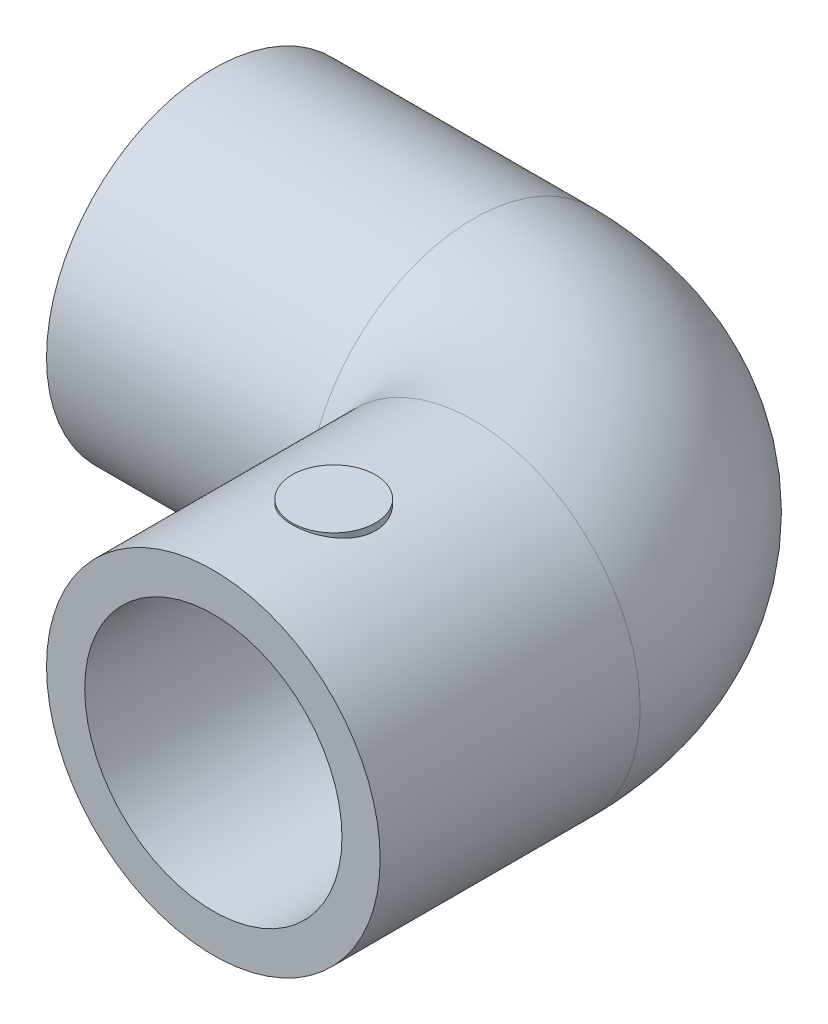
SolidWorks part; units mm, degrees
material "PVC Rígido"
ref_plane "Alzado" through (0, 0, 0) normal (0, 0, 1) x (1, 0, 0)
ref_plane "Planta" through (0, 0, 0) normal (0, 1, 0) x (1, 0, 0)
ref_plane "Vista lateral" through (0, 0, 0) normal (1, 0, 0) x (0, 0, -1)
sketch "Croquis1" plane through (0, 0, 0) normal (0, 1, 0) x (1, 0, 0)
  line L0 (-36.125, 0) -> (-14.5, 0)
  line L1 (0, -14.5) -> (0, -36.125)
  arc A0 (-14.5, 0) -> (0, -14.5) centre (-14.5, -14.5) cw
  point P6 (0, 0)
  dimension "D3" = 14.5
  dimension "D1" = 36.125
  dimension "D2" = 36.125
ref_plane "Plano1" through (0, 0, 36.125) normal (0, 0, 1) x (1, 0, 0)
sketch "Croquis2" plane through (0, 0, 36.125) normal (0, 0, 1) x (1, 0, 0)
  circle A0 centre (0, 0) radius 13.875
  circle A1 centre (0, 0) radius 10.7
  dimension "D1" = 27.75
  dimension "D2" = 21.4
sweep "Barrer1" add profiles "Croquis2" path "Croquis1"
sketch "Croquis3" plane through (0, 0, 36.125) normal (0, 0, 1) x (1, 0, 0)
  circle A0 centre (0, 0) radius 10.0034
  circle A1 centre (0, 0) radius 10.7
  circle A2 centre (0, 0) radius 10.7 construction
extrude "Saliente-Extruir1" add sketch "Croquis3" against normal blind 1 from offset 22.5 offset against normal yes
sketch "Croquis5" plane through (-36.125, 0, 0) normal (-1, 0, 0) x (0, 0, 1)
  circle A0 centre (0, 0) radius 9.6972
  circle A1 centre (0, 0) radius 10.7
  circle A2 centre (0, 0) radius 10.7 construction
extrude "Saliente-Extruir2" add sketch "Croquis5" along normal blind 1 from offset 22.5 offset against normal yes
sketch "Croquis6" plane through (0, 0, 0) normal (0, 1, 0) x (1, 0, 0)
  circle A0 centre (0, -26.1093) radius 3.4666
extrude "Saliente-Extruir3" add sketch "Croquis6" against normal blind 1 from offset 14
